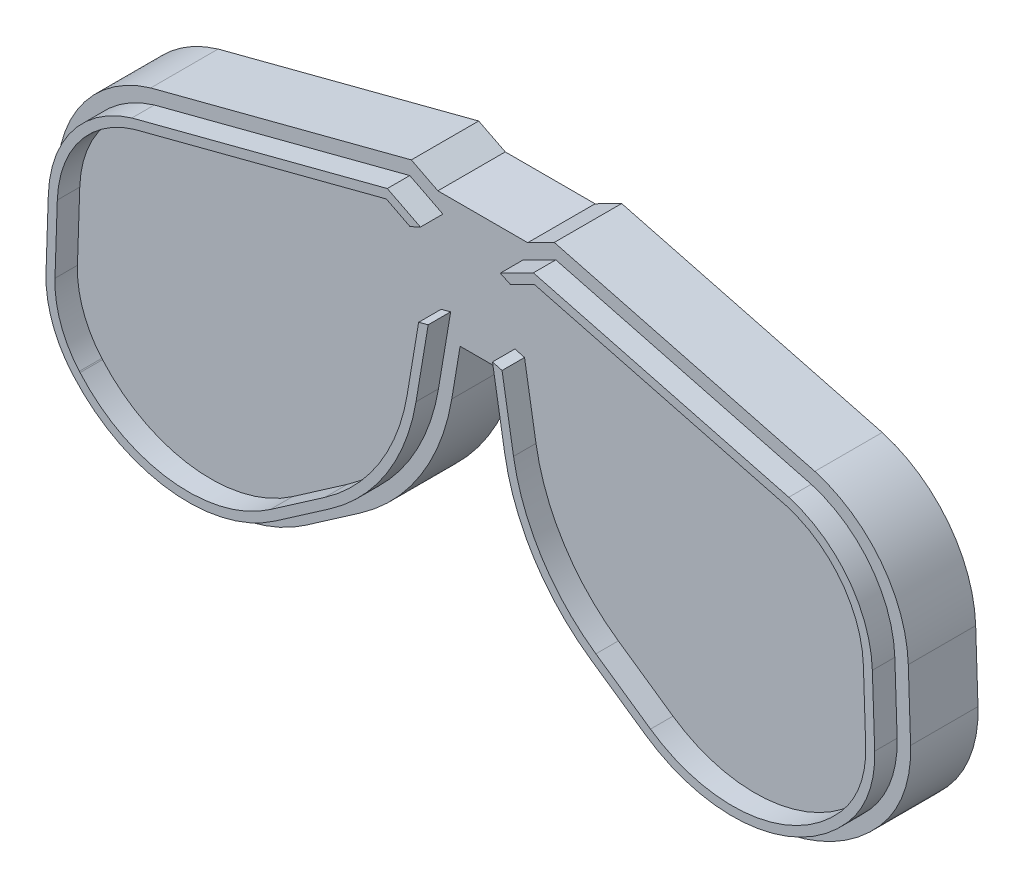
SolidWorks part; units mm, degrees
ref_plane "Front Plane" through (0, 0, 0) normal (0, 0, 1) x (1, 0, 0)
ref_plane "Top Plane" through (0, 0, 0) normal (0, 1, 0) x (1, 0, 0)
ref_plane "Right Plane" through (0, 0, 0) normal (1, 0, 0) x (0, 0, -1)
sketch "Sketch2" plane through (0, 0, 0) normal (0, 0, 1) x (1, 0, 0)
  line L0 (77.6667, 150) -> (388.3333, 150) construction
  line L9 (13.6071, 110.9778) -> (13.2123, 111.4293)
  line L10 (-3.7003, 158.8773) -> (-2.3893, 197.8301)
  line L11 (50.44, 266.0177) -> (197.7702, 304.4461)
  line L12 (197.7702, 304.4461) -> (212.7827, 296.8135)
  line L14 (225.3527, 226.994) -> (220.6363, 198.7801)
  line L15 (168.7902, 117.0169) -> (137.902, 95.603)
  line L23 (212.7827, 296.8135) -> (263.5827, 296.8135)
  line L27 (238.1827, 226.994) -> (238.1827, 83.3839) construction
  line L29 (238.1827, 296.8135) -> (238.1827, 354.7702) construction
  line L31 (278.5953, 304.4461) -> (263.5827, 296.8135)
  line L32 (425.9254, 266.0177) -> (278.5953, 304.4461)
  line L34 (251.0128, 226.994) -> (255.7292, 198.7801)
  line L35 (480.0658, 158.8773) -> (478.7547, 197.8301)
  line L36 (462.7584, 110.9778) -> (463.1531, 111.4293)
  line L37 (307.5753, 117.0169) -> (338.4634, 95.603)
  line L38 (225.3527, 226.994) -> (251.0128, 226.994)
  line L39 (23.1679, 119.3372) -> (22.7732, 119.7887)
  line L40 (8.9925, 158.4501) -> (10.3036, 197.4029)
  line L41 (53.8447, 253.7808) -> (196.3113, 290.9407)
  line L42 (196.3113, 290.9407) -> (209.7396, 284.1135)
  line L51 (214.5994, 239.694) -> (208.1101, 200.874)
  line L52 (161.5544, 127.454) -> (130.6662, 106.0401)
  line L71 (52.4805, 258.675) -> (196.8948, 296.3428)
  line L72 (209.7396, 284.1135) -> (266.6258, 284.1135) construction
  line L75 (214.5994, 239.694) -> (261.766, 239.694) construction
  line L76 (196.8948, 296.3428) -> (215.6134, 286.826)
  line L85 (219.9982, 241.1793) -> (213.1205, 200.0364)
  line L86 (164.4487, 123.2792) -> (133.5605, 101.8652)
  line L87 (19.3436, 115.9934) -> (18.9488, 116.4449)
  line L88 (3.9153, 158.621) -> (5.2264, 197.5738)
  line L89 (56.5839, 243.9954) -> (195.1442, 280.1363) construction
  line L90 (19.1467, 158.1083) -> (20.4578, 197.0611) construction
  line L91 (155.7658, 135.8037) -> (124.8776, 114.3898) construction
  line L92 (207.0943, 256.4193) -> (198.0891, 202.5492) construction
  line L93 (207.0943, 256.4193) -> (219.9982, 241.1793) construction
  line L94 (195.1442, 280.1363) -> (211.9617, 271.586) construction
  line L95 (211.9617, 271.586) -> (215.6134, 286.826) construction
  line L96 (195.7277, 285.5385) -> (208.5224, 279.0335) construction
  line L97 (208.5224, 279.0335) -> (209.7396, 284.1135) construction
  line L98 (55.2123, 248.8876) -> (195.7277, 285.5385) construction
  line L99 (14.0696, 158.2792) -> (15.3807, 197.232) construction
  line L100 (158.6601, 131.6289) -> (127.7719, 110.2149) construction
  line L101 (210.2981, 244.774) -> (203.0996, 201.7116) construction
  line L102 (210.2981, 244.774) -> (214.5994, 239.694) construction
  line L103 (209.7396, 284.1135) -> (215.6134, 286.826)
  line L104 (214.5994, 239.694) -> (219.9982, 241.1793)
  line L105 (261.766, 239.694) -> (268.2554, 200.874)
  line L106 (422.5208, 253.7808) -> (280.0542, 290.9407) construction
  line L109 (280.0542, 290.9407) -> (266.6258, 284.1135) construction
  line L111 (261.766, 239.694) -> (268.2554, 200.874) construction
  line L113 (314.811, 127.454) -> (345.6992, 106.0401) construction
  line L115 (467.373, 158.4501) -> (466.0619, 197.4029) construction
  line L117 (453.1975, 119.3372) -> (453.5923, 119.7887) construction
  line L118 (314.811, 127.454) -> (345.6992, 106.0401)
  line L119 (453.1975, 119.3372) -> (453.5923, 119.7887)
  line L120 (467.373, 158.4501) -> (466.0619, 197.4029)
  line L121 (422.5208, 253.7808) -> (280.0542, 290.9407)
  line L122 (280.0542, 290.9407) -> (266.6258, 284.1135)
  line L123 (266.6258, 284.1135) -> (260.752, 286.826)
  line L124 (279.4706, 296.3428) -> (260.752, 286.826)
  line L125 (423.8849, 258.675) -> (279.4706, 296.3428)
  line L126 (472.4501, 158.621) -> (471.139, 197.5738)
  line L127 (457.0219, 115.9934) -> (457.4166, 116.4449)
  line L128 (311.9167, 123.2792) -> (342.8049, 101.8652)
  line L129 (256.3672, 241.1793) -> (263.2449, 200.0364)
  line L130 (261.766, 239.694) -> (256.3672, 241.1793)
  line L131 (30.8166, 126.0248) -> (30.4218, 126.4763) construction
  line L132 (26.9923, 122.681) -> (26.5975, 123.1325) construction
  arc A5 (137.902, 95.603) -> (13.6071, 110.9778) centre (84.3573, 172.8377) cw
  arc A6 (13.2123, 111.4293) -> (-3.7003, 158.8773) centre (64.8408, 156.5703) cw
  arc A7 (50.44, 266.0177) -> (-2.3893, 197.8301) centre (71.2291, 195.3522) ccw
  arc A9 (220.6363, 198.7801) -> (168.7902, 117.0169) centre (97.8796, 219.3007) cw
  arc A16 (255.7292, 198.7801) -> (307.5753, 117.0169) centre (378.4858, 219.3007) ccw
  arc A17 (425.9254, 266.0177) -> (478.7547, 197.8301) centre (405.1364, 195.3522) cw
  arc A18 (463.1531, 111.4293) -> (480.0658, 158.8773) centre (411.5246, 156.5703) ccw
  arc A19 (338.4634, 95.603) -> (462.7584, 110.9778) centre (392.0082, 172.8377) ccw
  arc A20 (130.6662, 106.0401) -> (23.1679, 119.3372) centre (84.3573, 172.8377) cw
  arc A21 (22.7732, 119.7887) -> (8.9925, 158.4501) centre (64.8408, 156.5703) cw
  arc A22 (53.8447, 253.7808) -> (10.3036, 197.4029) centre (71.2291, 195.3522) ccw
  arc A27 (208.1101, 200.874) -> (161.5544, 127.454) centre (97.8796, 219.3007) cw
  arc A40 (213.1205, 200.0364) -> (164.4487, 123.2792) centre (97.8796, 219.3007) cw
  arc A41 (133.5605, 101.8652) -> (19.3436, 115.9934) centre (84.3573, 172.8377) cw
  arc A42 (18.9488, 116.4449) -> (3.9153, 158.621) centre (64.8408, 156.5703) cw
  arc A43 (52.4805, 258.675) -> (5.2264, 197.5738) centre (71.2291, 195.3522) ccw
  arc A44 (56.5839, 243.9954) -> (20.4578, 197.0611) centre (71.2291, 195.3522) ccw construction
  arc A45 (30.4218, 126.4763) -> (19.1467, 158.1083) centre (64.8408, 156.5703) cw construction
  arc A46 (124.8776, 114.3898) -> (30.8166, 126.0248) centre (84.3573, 172.8377) cw construction
  arc A47 (198.0891, 202.5492) -> (155.7658, 135.8037) centre (97.8796, 219.3007) cw construction
  arc A48 (55.2123, 248.8876) -> (15.3807, 197.232) centre (71.2291, 195.3522) ccw construction
  arc A49 (26.5975, 123.1325) -> (14.0696, 158.2792) centre (64.8408, 156.5703) cw construction
  arc A50 (127.7719, 110.2149) -> (26.9923, 122.681) centre (84.3573, 172.8377) cw construction
  arc A51 (203.0996, 201.7116) -> (158.6601, 131.6289) centre (97.8796, 219.3007) cw construction
  arc A53 (268.2554, 200.874) -> (314.811, 127.454) centre (378.4858, 219.3007) ccw construction
  arc A55 (345.6992, 106.0401) -> (453.1975, 119.3372) centre (392.0082, 172.8377) ccw construction
  arc A57 (453.5923, 119.7887) -> (467.373, 158.4501) centre (411.5246, 156.5703) ccw construction
  arc A59 (422.5208, 253.7808) -> (466.0619, 197.4029) centre (405.1364, 195.3522) cw construction
  arc A60 (268.2554, 200.874) -> (314.811, 127.454) centre (378.4858, 219.3007) ccw
  arc A61 (345.6992, 106.0401) -> (453.1975, 119.3372) centre (392.0082, 172.8377) ccw
  arc A62 (453.5923, 119.7887) -> (467.373, 158.4501) centre (411.5246, 156.5703) ccw
  arc A63 (422.5208, 253.7808) -> (466.0619, 197.4029) centre (405.1364, 195.3522) cw
  arc A64 (423.8849, 258.675) -> (471.139, 197.5738) centre (405.1364, 195.3522) cw
  arc A65 (457.4166, 116.4449) -> (472.4501, 158.621) centre (411.5246, 156.5703) ccw
  arc A66 (342.8049, 101.8652) -> (457.0219, 115.9934) centre (392.0082, 172.8377) ccw
  arc A67 (263.2449, 200.0364) -> (311.9167, 123.2792) centre (378.4858, 219.3007) ccw
  point P126 (0, 0)
  point P127 (0, 0)
  point P128 (0, 0)
  point P129 (0, 0)
  dimension "D1" = 50.8
  dimension "D2" = 12.7
  dimension "D4" = 147.2331
  dimension "D5" = 5.08
  dimension "D6" = 149.246
extrude "Boss-Extrude4" add sketch "Sketch2" along normal blind 12.7 contours L129 A67 L128 A66 L127 A65 L126 A64 L125 L124 L123 L122 L121 A63 L120 A62 L119 A61 L118 A60 L105 L130 | L71 L76 L103 L42 L41 A22 L40 A21 L39 A20 L52 A27 L51 L104 L85 A40 L86 A41 L87 A42 L88 A43 region at (262.0395, 219.7873, 0)
extrude "Boss-Extrude5" add sketch "Sketch2<7>" against normal blind 38.1 separate body contours L37 A19 L36 A18 L35 A17 L32 L31 L23 L12 L11 A7 L10 A6 L9 A5 L15 A9 L14 L38 L34 A16 A67 L129 L130 L105 A60 L118 A61 L119 A62 L120 A63 L121 L122 L123 L124 L125 A64 L126 A65 L127 A66 L128 A43 L71 L76 L103 L42 | A22 L40 A21 L39 A20 L52 A27 L51 L104 L85 A40 L86 A41 L87 A42 L88 A43 L71 L76 L103 L42 L41 | A60 L118 A61 L119 A62 L120 A63 L121 L122 L123 L124 L125 A64 L126 A65 L127 A66 L128 A67 L129 L130 L105 region at (17.4286, 114.7174, 0)
sketch "Sketch2<7>" plane through (0, 0, 0) normal (0, 0, 1) x (1, 0, 0) same geometry as "Sketch2"
